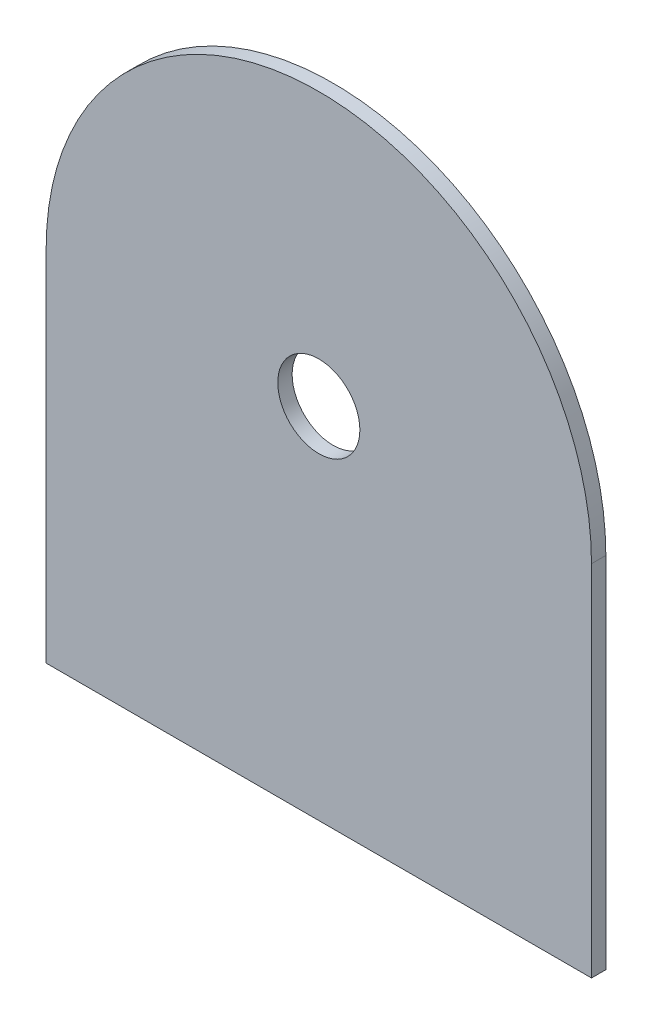
SolidWorks part; units mm, degrees
material "201 Annealed Stainless Steel (SS)"
ref_plane "Front Plane" through (0, 0, 0) normal (0, 0, 1) x (1, 0, 0)
ref_plane "Top Plane" through (0, 0, 0) normal (0, 1, 0) x (1, 0, 0)
ref_plane "Right Plane" through (0, 0, 0) normal (1, 0, 0) x (0, 0, -1)
sketch "Plate shape" plane through (0, 0, 0) normal (0, 0, 1) x (1, 0, 0)
  line L0 (-95, 0) -> (95, 0)
  line L1 (95, 0) -> (95, 125)
  line L2 (-95, 0) -> (-95, 125)
  line L3 (0, 30) -> (95, 30) construction
  arc A0 (-95, 125) -> (95, 125) centre (0, 125) cw
  arc A1 (95, 125) -> (-95, 125) centre (0, 125) cw construction
  point P3 (0, 0)
  dimension "D1" = 95
  dimension "D2" = 30
  dimension "D3" = 190
extrude "Outer casing" add sketch "Plate shape" along normal blind 5
sketch "Sketch1" plane through (0, 0, 5) normal (0, 0, 1) x (1, 0, 0)
  circle A0 centre (0, 125) radius 95 construction
  arc A1 (95, 125) -> (-95, 125) centre (0, 125) ccw construction
  circle A2 centre (0, 125) radius 14.3
  dimension "D1" = 28.6
extrude "Inner Cutout" cut sketch "Sketch1" against normal blind 10
sketch "Sketch2" plane through (0, 0, 0) normal (1, 0, 0) x (0, 0, -1)
  line L0 (-5, 110.7) -> (0, 110.7) construction
  point P3 (-2.5, 110.7)
  point P4 (-2.5, 110.7)
ref_plane "Plane1" through (0, 0, 2.5) normal (0, 0, 1) x (1, 0, 0)
sketch "Sketch3" plane through (0, 0, 2.5) normal (0, 0, 1) x (1, 0, 0)
  circle A0 centre (0, 125) radius 14.3 construction
  circle A1 centre (0, 125) radius 14.3 construction
